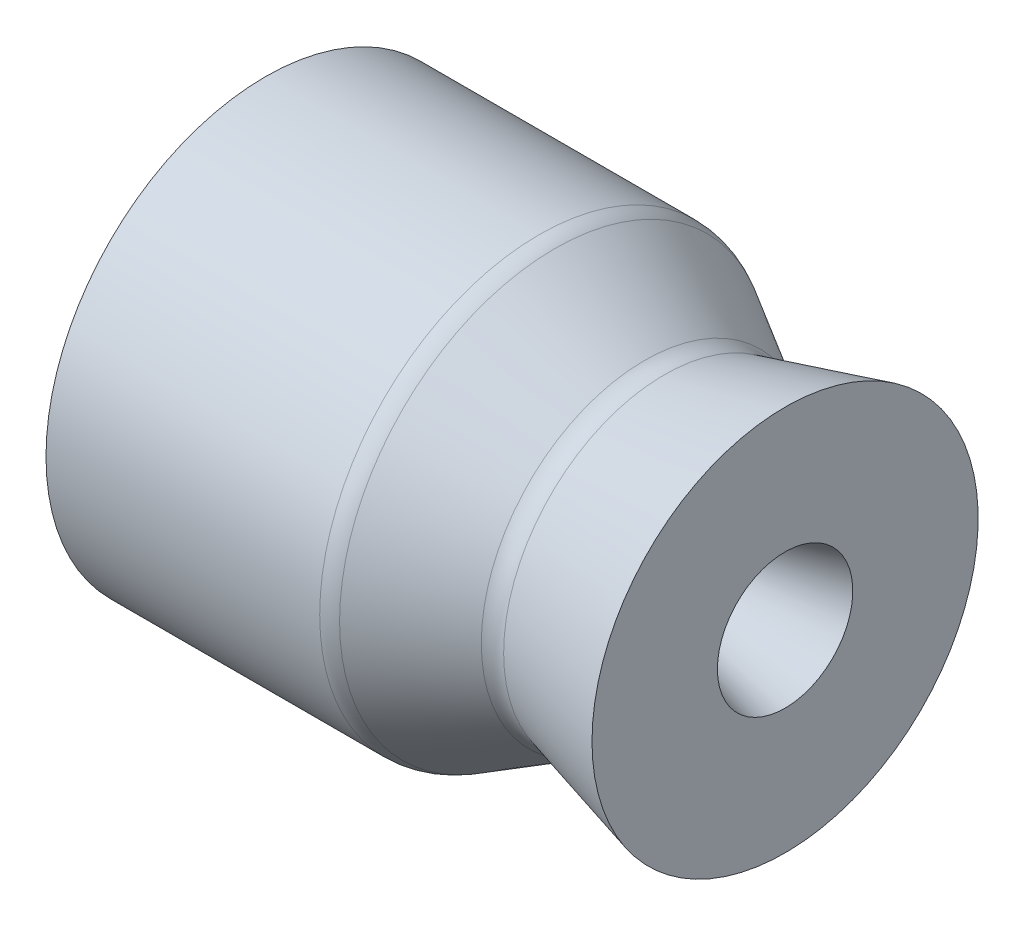
SolidWorks part; units mm, degrees
material "AISI 304"
ref_plane "Front Plane" through (0, 0, 0) normal (0, 0, 1) x (1, 0, 0)
ref_plane "Top Plane" through (0, 0, 0) normal (0, 1, 0) x (1, 0, 0)
ref_plane "Right Plane" through (0, 0, 0) normal (1, 0, 0) x (0, 0, -1)
sketch "chamberNozzle" plane through (0, 0, 0) normal (0, 0, 1) x (1, 0, 0)
  line L0 (0, 0) -> (366.3783, 0) construction
  line L1 (0, 0) -> (0, 38.1) construction
  line L2 (0, 38.1) -> (110.897, 38.1)
  line L3 (158.9188, 24.511) -> (158.9188, 13.97) construction
  line L4 (117.247, 36.3985) -> (153.6483, 15.3822)
  line L5 (150.9294, 13.97) -> (106.9103, 13.97) construction
  line L6 (161.647, 14.3292) -> (210.5452, 27.4314)
  line L7 (210.5452, 27.4314) -> (210.5452, 0) construction
  line L8 (0, 88.9) -> (110.897, 88.9)
  line L9 (117.247, 87.1985) -> (153.6483, 66.1822)
  line L10 (161.647, 65.1292) -> (210.5452, 78.2314)
  line L11 (0, 38.1) -> (0, 45.72)
  line L12 (0, 45.72) -> (5.08, 45.72)
  line L13 (5.08, 45.72) -> (5.08, 55.88)
  line L14 (5.08, 55.88) -> (0, 55.88)
  line L15 (0, 55.88) -> (0, 88.9)
  line L17 (210.5452, 78.2314) -> (210.5452, 27.4314)
  arc A0 (153.6483, 15.3822) -> (161.647, 14.3292) centre (158.9188, 24.511) ccw
  arc A1 (110.897, 38.1) -> (117.247, 36.3985) centre (110.897, 25.4) cw
  arc A2 (153.6483, 66.1822) -> (161.647, 65.1292) centre (158.9188, 75.311) ccw
  arc A3 (110.897, 88.9) -> (117.247, 87.1985) centre (110.897, 76.2) cw
  point P16 (114.3, 38.1)
  point P28 (5.08, 50.8)
  dimension "D4" = 21.082
  dimension "D9" = 12.7
  dimension "D1" = 38.1
  dimension "D3" = 13.97
  dimension "D5" = 30
  dimension "D6" = 15
  dimension "D10" = 50.8
  dimension "D11" = 10.16
  dimension "D12" = 5.08
  dimension "D13" = 12.7
revolve "Revolve1" add sketch "chamberNozzle" angle 360 about L0
ref_plane "chamberInterface" through (0, 0, 0) normal (-1, 0, 0) x (0, 0, 1)
sketch "Sketch1" plane through (0, 0, 0) normal (-1, 0, 0) x (0, 0, 1)
  line L0 (0, 55.88) -> (0, 88.9) construction
  circle A0 centre (0, 0) radius 72.39 construction
  circle A1 centre (0, 0) radius 55.88 construction
  circle A2 centre (0, 0) radius 88.9 construction
  point P10 (0, 72.39)
hole_wizard "1/2 (0.5) Diameter Hole1" positions "Sketch2" profile "Sketch3" hole size "1/2" standard "ANSI Inch"
sketch "Sketch2" plane through (0, 0, 0) normal (-1, 0, 0) x (0, 0, 1)
  circle A0 centre (0, 0) radius 72.39 construction
  point P0 (-72.39, 0)
sketch "Sketch3" plane through (0, 0, -72.39) normal (0, 1, 0) x (0, 0, 1)
  line L0 (0, 0) -> (0, 16.5155)
  line L1 (0, 16.5155) -> (6.35, 12.7)
  line L2 (6.35, 12.7) -> (6.35, 0.635)
  line L3 (6.35, 0.635) -> (6.985, 0)
  line L5 (6.985, 0) -> (0, 0)
  line L6 (-6.35, 0.635) -> (-6.985, 0) construction
  line L10 (0, 16.5155) -> (-6.35, 12.7) construction
  line L11 (0, -6.35) -> (0, 107.95) construction
  dimension "Hole Dia." = 12.7
  dimension "Hole Depth" = 12.7
  dimension "Near C'Sink Dia." = 13.97
  dimension "Near C'Sink Angle" = 90
  dimension "Drill Angle" = 118
pattern_circular "CirPattern1" count 6 over 360 about axis through (0, 0, 0) along (-1, 0, 0) of "1/2 (0.5) Diameter Hole1"
equation "\"l_star\"= .8m'characteristic length"
equation "\"R_t\"= .55in'throat radius"
equation "\"V_c\"= \"l_star\" * \"R_t\"'chamber volume"
equation "\"D_c\"= 3in'chamber diameter"
equation "\"L_c\"= \"V_c\" / ( ( pi * \"D_c\" ) / 4 )'chamber length"
equation "\"eps_x\"= 3.8557'expansion ratio"
equation "\"D_e\"= \"R_t\" * 2 * sqr ( \"eps_x\" )'exit diameter"
equation "\"arc_t\"= 1.5in * \"R_t\"'arc between convergent and divergent"
equation "\"D3@chamberNozzle\" = \"R_t\""
equation "\"D7@chamberNozzle\" = \"D_e\" / 2"
equation "\"D1@chamberNozzle\" = \"D_c\" / 2"
equation "\"D12@chamberNozzle\"=\"D11@chamberNozzle\"/2"
equation "\"D13@chamberNozzle\"=\"D10@chamberNozzle\"/4"
